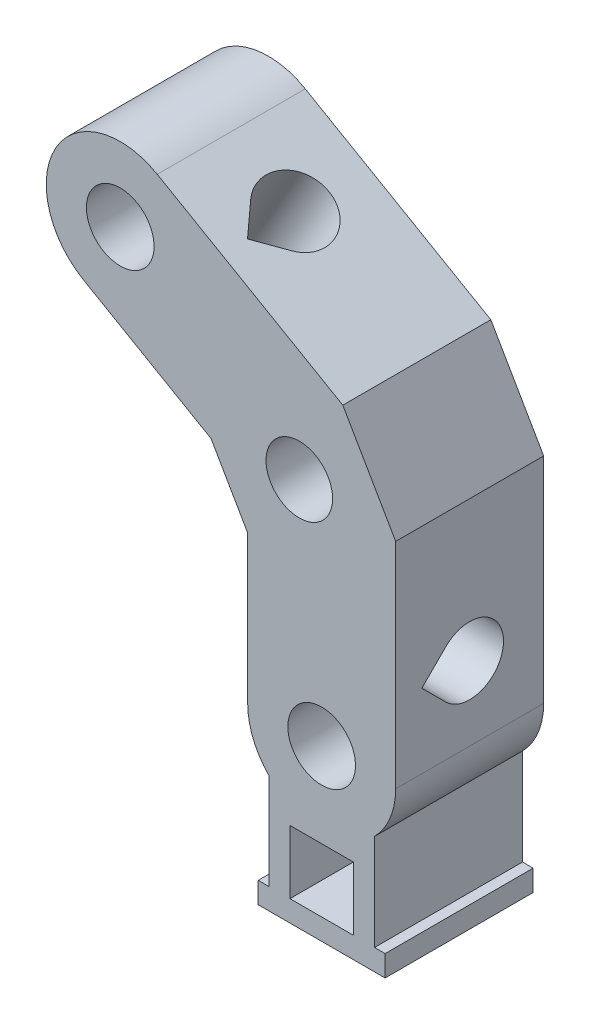
SolidWorks part; units mm, degrees
ref_plane "Front Plane" through (0, 0, 0) normal (0, 0, 1) x (1, 0, 0)
ref_plane "Top Plane" through (0, 0, 0) normal (0, 1, 0) x (1, 0, 0)
ref_plane "Right Plane" through (0, 0, 0) normal (1, 0, 0) x (0, 0, -1)
ref_plane "Plane4" through (0, 0, 14) normal (0, 0, 1) x (1, 0, 0)
sketch "Sketch1" plane through (0, 0, 14) normal (0, 0, 1) x (1, 0, 0)
  line L0 (7, 0) -> (7, 20.2679)
  line L1 (7, 20.2679) -> (2, 28.9282)
  line L2 (2, 28.9282) -> (-15.5526, 39.0622)
  line L3 (-22.5526, 26.9378) -> (-10.4641, 19.9585)
  line L4 (-10.4641, 19.9585) -> (-7, 13.9585)
  line L5 (-7, 13.9585) -> (-7, 0)
  line L6 (-8.7321, 16.9585) -> (4.5, 24.5981) construction
  line L7 (0, 0) -> (0, -16) construction
  line L8 (-6, -14) -> (-5, -14)
  line L9 (-6, -14) -> (-6, -16)
  line L10 (-6, -16) -> (6, -16)
  line L11 (6, -14) -> (6, -16)
  line L13 (-5, -14) -> (-5, -4.899)
  line L14 (5, -14) -> (6, -14)
  line L15 (5, -14) -> (5, -4.899)
  line L16 (-3, -14) -> (3, -14)
  line L17 (-3, -14) -> (-3, -8)
  line L18 (-3, -8) -> (3, -8)
  line L19 (3, -14) -> (3, -8)
  arc A0 (-15.5526, 39.0622) -> (-22.5526, 26.9378) centre (-19.0526, 33) ccw
  arc A1 (-7, 0) -> (-5, -4.899) centre (0, 0) ccw
  arc A2 (5, -4.899) -> (7, 0) centre (0, 0) ccw
  dimension "D2" = 7
  dimension "D1" = 120
  dimension "D3" = 150
  dimension "D4" = 10
  dimension "D5" = 38.1051
  dimension "D6" = 12
  dimension "D7" = 10
  dimension "D8" = 6
  dimension "D9" = 6
  dimension "D10" = 3
  dimension "D11" = 16
  dimension "D12" = 2
  dimension "D13" = 5
extrude "Boss-Extrude1" add sketch "Sketch1" against normal blind 14
hole_wizard "Hole2" positions "Sketch7" profile "Sketch6" legacy
sketch "Sketch7" plane through (0, 0, 0) normal (0, 0, -1) x (-1, 0, 0)
  line L0 (0, 0) -> (19.0525, 32.9999) construction
  line L2 (0, 0) -> (22.3725, 0) construction
  point P0 (19.0525, 32.9999)
  dimension "D1" = 38.105
  dimension "D2" = 60
sketch "Sketch6" plane through (-19.0525, 32.9999, 0) normal (1, 0, 0) x (0, 1, 0)
  line L0 (0, 0) -> (0, 14)
  line L1 (0, 14) -> (3.2, 14)
  line L2 (3.2, 14) -> (3.2, 0)
  line L3 (3.2, 0) -> (0, 0)
  line L4 (0, 110) -> (0, -10) construction
  dimension "Diameter" = 6.4
  dimension "Depth" = 14
hole_wizard "Hole1" positions "Sketch5" profile "Sketch4" legacy end condition through all
sketch "Sketch5" plane through (0, 0, 0) normal (0, 0, -1) x (-1, 0, 0)
  point P0 (0, 0)
sketch "Sketch4" plane through (0, 0, 0) normal (1, 0, 0) x (0, 1, 0)
  line L0 (0, 0) -> (0, 14)
  line L1 (0, 14) -> (3.2, 14)
  line L2 (3.2, 14) -> (3.2, 0)
  line L3 (3.2, 0) -> (0, 0)
  line L4 (0, 110) -> (0, -10) construction
  dimension "Diameter" = 6.4
  dimension "Depth" = 14
ref_axis "Axis1" through (-19.0525, 32.9999, 14) along (0, 0, -1)
sketch "Sketch3" plane through (-7, 0, 0) normal (-1, 0, 0) x (0, 0, 1)
  line L0 (9.2627, 4.7373) -> (11.5255, 7)
  line L1 (11.5255, 7) -> (9.2627, 9.2627)
  line L2 (0, 13.9585) -> (0, 0) construction
  line L3 (7, 7) -> (7, 0) construction
  line L4 (0, 0) -> (14, 0) construction
  arc A0 (9.2627, 9.2627) -> (9.2627, 4.7373) centre (7, 7) ccw
  dimension "D1" = 3.2
  dimension "D2" = 45
  dimension "D3" = 7
extrude "Cut-Extrude2" cut sketch "Sketch3" against normal through all
sketch "Sketch2" plane through (6.0263, 10.4378, 0) normal (-0.5, -0.866, 0) x (0.866, -0.5, 0)
  line L0 (-25.9999, 11.5255) -> (-28.2626, 9.2627)
  line L1 (-23.7372, 9.2627) -> (-25.9999, 11.5255)
  line L2 (-25.9999, 7) -> (-33, 7) construction
  line L3 (-33, 0) -> (-33, 14) construction
  line L4 (-32.9999, 14) -> (-32.9999, 0) construction
  arc A0 (-28.2626, 9.2627) -> (-23.7372, 9.2627) centre (-25.9999, 7) ccw
  dimension "D1" = 7
  dimension "D3" = 3.2
  dimension "D2" = 45
extrude "Cut-Extrude1" cut sketch "Sketch2" against normal through all
sketch "Sketch8" plane through (0, 0, 14) normal (0, 0, 1) x (1, 0, 0)
  line L0 (-8.7321, 16.9585) -> (4.5, 24.5981) construction
  line L1 (-10.4641, 19.9585) -> (-7, 13.9585) construction
  line L2 (7, 20.2679) -> (2, 28.9282) construction
  circle A0 centre (-2.116, 20.7783) radius 3.15
  dimension "D1" = 6.3
extrude "Cut-Extrude3" cut sketch "Sketch8" against normal through all
equation "\"vHole_Dia\"=6.4"
equation "\"Diameter@Sketch4\"=\"vHole_Dia\""
equation "\"Diameter@Sketch6\"=\"vHole_Dia\""
equation "\"D1@Sketch3\"=\"hHole_Dia\"/2"
equation "\"D3@Sketch2\"=\"hHole_Dia\"/2"
equation "\"hHole_Dia\"=6.4"
